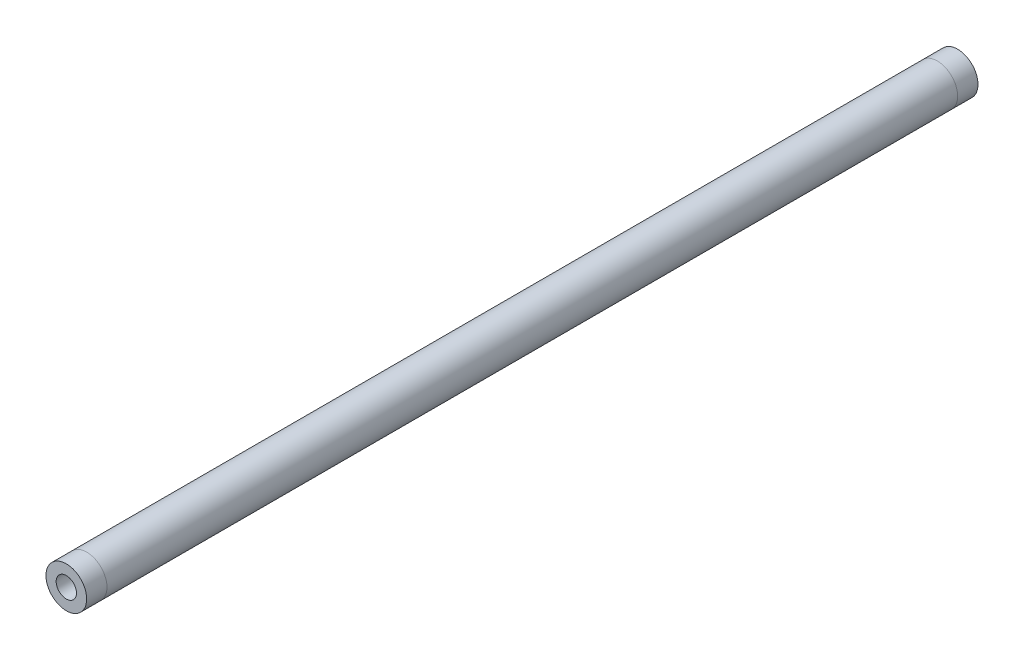
SolidWorks part; units mm, degrees
material "AISI 4130 Steel, normalized at 870C"
ref_plane "Front Plane" through (0, 0, 0) normal (0, 0, 1) x (1, 0, 0)
ref_plane "Top Plane" through (0, 0, 0) normal (0, 1, 0) x (1, 0, 0)
ref_plane "Right Plane" through (0, 0, 0) normal (1, 0, 0) x (0, 0, -1)
sketch "Axis" plane through (0, 0, 0) normal (0, 1, 0) x (1, 0, 0)
  line L0 (0, 0) -> (0, 21.9075) construction
  line L1 (0, 21.9075) -> (0, 300.0818) construction
  line L2 (0, 300.0818) -> (0, 321.9893) construction
  dimension "D1" = 21.9075
  dimension "D2" = 321.9893
sketch "Sketch2" plane through (0, 0, 0) normal (0, 0, 1) x (1, 0, 0)
  circle A0 centre (0, 0) radius 6.35
  circle A1 centre (0, 0) radius 3.175
  circle A2 centre (0, 0) radius 4.7625
  point P6 (0, 0)
  dimension "D1" = 12.7
  dimension "D2" = 6.35
  dimension "D3" = 9.525
extrude "Threaded Insert 1-1" add sketch "Sketch2" against normal blind 6.35 from vertex contours A0 A2 | A2 A1 region at (-6.1704, 0, 0) region at (-4.6278, 0, 0) starting at point (0, 0, -21.9075)
extrude "Threaded Insert 1-2" add sketch "Sketch2<5>" against normal blind 9.525 from surface contours A2 A1 region at (-4.6278, 0, 0) starting at face at (6.35, 0, -28.2575)
sketch "Sketch2<5>" plane through (0, 0, 0) normal (0, 0, 1) x (1, 0, 0) same geometry as "Sketch2"
extrude "Boss-Extrude4" add sketch "Sketch2<7>" along normal blind 6.35 from vertex separate body contours A0 A2 | A2 A1 region at (-6.1704, 0, 0) region at (-4.6278, 0, 0) starting at point (0, 0, -300.0818)
sketch "Sketch2<7>" plane through (0, 0, 0) normal (0, 0, 1) x (1, 0, 0) same geometry as "Sketch2"
extrude "Boss-Extrude5" add sketch "Sketch2<8>" along normal blind 9.525 from surface contours A2 A1 region at (-4.6278, 0, 0) starting at face at (6.35, 0, -293.7318)
sketch "Sketch2<8>" plane through (0, 0, 0) normal (0, 0, 1) x (1, 0, 0) same geometry as "Sketch2"
extrude "Boss-Extrude6" add sketch "Sketch2<9>" against normal up to surface (293.7318 mm away) from surface separate body contours A0 A2 region at (-6.1704, 0, 0) up to face at (6.35, 0, -293.7318) starting at face at (4.7625, 0, -28.2575)
sketch "Sketch2<9>" plane through (0, 0, 0) normal (0, 0, 1) x (1, 0, 0) same geometry as "Sketch2"
equation "\"Tube Outer Diameter\"= .5"
equation "\"Tube Inner Diameter\"= .375"
equation "\"Rod end Diameter\"= .25"
equation "\"Threaded Insert Out\"= .25"
equation "\"Threaded Insert In\"= .375'`"
equation "\"D1@Sketch2\"=\"Tube Outer Diameter\""
equation "\"D2@Sketch2\"=\"Rod end Diameter\""
equation "\"D1@Threaded Insert 1-1\" = \"Threaded Insert Out\""
equation "\"D3@Sketch2\"=\"Tube Inner Diameter\""
equation "\"D1@Threaded Insert 1-2\" = \"Threaded Insert In\""
equation "\"D1@Boss-Extrude4\"=\"Threaded Insert Out\""
equation "\"D1@Boss-Extrude5\"=\"Threaded Insert In\""
